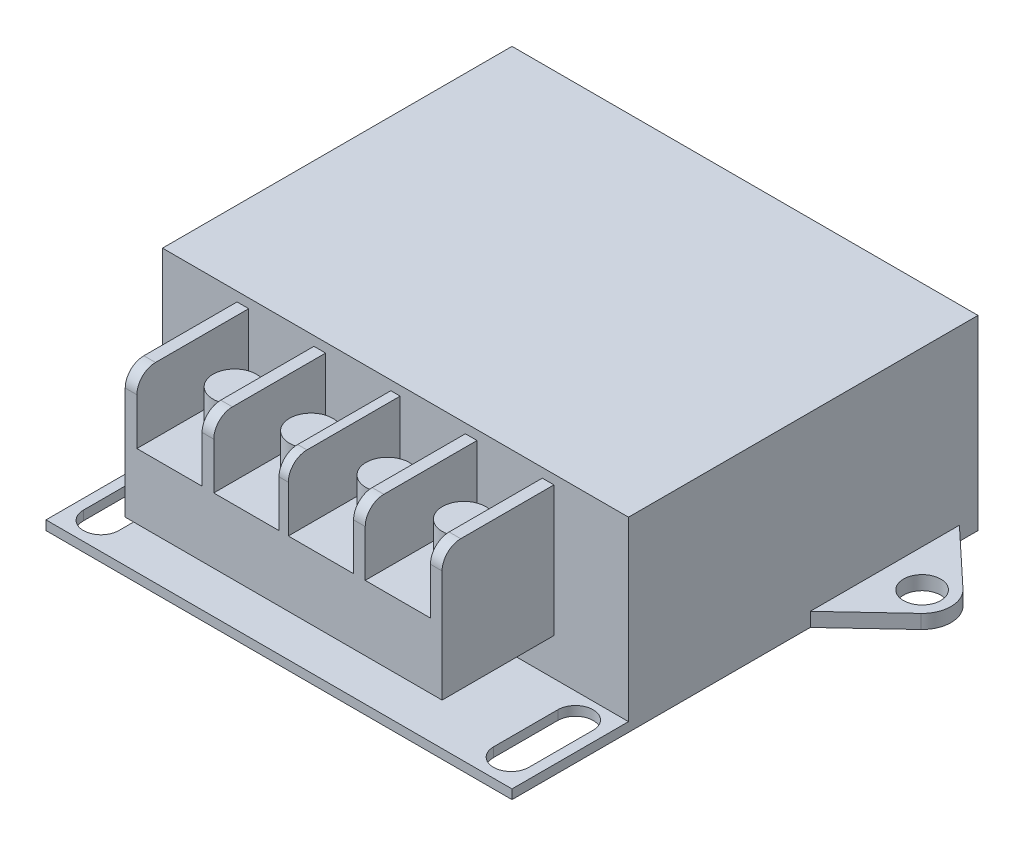
SolidWorks part; units mm, degrees
ref_plane "Front Plane" through (0, 0, 0) normal (0, 0, 1) x (1, 0, 0)
ref_plane "Top Plane" through (0, 0, 0) normal (0, 1, 0) x (1, 0, 0)
ref_plane "Right Plane" through (0, 0, 0) normal (1, 0, 0) x (0, 0, -1)
sketch "Sketch1" plane through (0, 0, 0) normal (0, 1, 0) x (1, 0, 0)
  line L1 (0, 0) -> (50, 0)
  line L2 (0, 0) -> (0, 50)
  line L3 (0, 50) -> (50, 50)
  line L4 (50, 0) -> (50, 50)
  dimension "D1" = 50
  dimension "D2" = 50
extrude "Boss-Extrude1" add sketch "Sketch1" along normal blind 1
sketch "Sketch2" plane through (0, 1, 0) normal (0, 1, 0) x (1, 0, 0)
  line L0 (50, 0) -> (50, 50) construction
  line L1 (0, 50) -> (50, 50)
  line L2 (0, 50) -> (0, 12.5)
  line L3 (0, 12.5) -> (50, 12.5)
  line L4 (50, 50) -> (50, 12.5)
  dimension "D1" = 37.5
extrude "Boss-Extrude2" add sketch "Sketch2" along normal blind 19
sketch "Sketch3" plane through (0, 0, -12.5) normal (0, 0, 1) x (1, 0, 0)
  line L0 (0, 20) -> (50, 20) construction
  line L1 (8, 19) -> (42, 19)
  line L2 (8, 19) -> (8, 5)
  line L3 (8, 5) -> (42, 5)
  line L4 (42, 19) -> (42, 5)
  point P4 (25, 20)
  point P5 (25, 19)
  dimension "D1" = 34
  dimension "D2" = 14
  dimension "D3" = 1
extrude "Boss-Extrude3" add sketch "Sketch3" along normal blind 12
sketch "Sketch4" plane through (0, 0, 0) normal (0, -1, 0) x (1, 0, 0)
  line L0 (0, -50) -> (0, 0) construction
  line L2 (-6.1215, -37.7396) -> (0, -32.0038)
  line L3 (-6.1215, -42.2679) -> (0, -48.0038)
  circle A0 centre (-4, -40.0038) radius 2
  arc A2 (-6.1215, -37.7396) -> (-6.1215, -42.2679) centre (-4, -40.0038) ccw
  point P4 (-7, -40.7957)
  line M6 (0, 0) -> (0, -50)
  dimension "D1" = 4
  dimension "D2" = 4
  dimension "D3" = 16
  dimension "D4" = 7
extrude "Boss-Extrude4" add sketch "Sketch4" against normal blind 1.5 contours L2 A2 L3 A0 M6 region at (-2.9411, 0, -34.9994)
ref_plane "Plane1" through (25, 0, 0) normal (-1, 0, 0) x (0, 0, 1)
mirror "Mirror1" about plane through (25, 0, 0) normal (-1, 0, 0) of "Boss-Extrude4"
sketch "Sketch5" plane through (0, 19, 0) normal (0, 1, 0) x (1, 0, 0)
  line L0 (42, 0.5) -> (8, 0.5) construction
  line L1 (9.25, 0.5) -> (16.25, 0.5)
  line L2 (9.25, 0.5) -> (9.25, 12.5)
  line L3 (9.25, 12.5) -> (16.25, 12.5)
  line L4 (16.25, 0.5) -> (16.25, 12.5)
  line L5 (8, 0.5) -> (8, 12.5) construction
  line L6 (17.5, 0.5) -> (24.5, 0.5)
  line L7 (17.5, 0.5) -> (17.5, 12.5)
  line L8 (17.5, 12.5) -> (24.5, 12.5)
  line L9 (24.5, 0.5) -> (24.5, 12.5)
  line L10 (25.5, 0.5) -> (32.5, 0.5)
  line L11 (25.5, 0.5) -> (25.5, 12.5)
  line L12 (25.5, 12.5) -> (32.5, 12.5)
  line L13 (32.5, 0.5) -> (32.5, 12.5)
  line L14 (33.75, 0.5) -> (40.75, 0.5)
  line L15 (33.75, 0.5) -> (33.75, 12.5)
  line L16 (33.75, 12.5) -> (40.75, 12.5)
  line L17 (40.75, 0.5) -> (40.75, 12.5)
  line L18 (42, 0.5) -> (42, 12.5) construction
  line L19 (0, 12.5) -> (50, 12.5) construction
  line M16 (42, 12.5) -> (8, 12.5)
  line M18 (8, 0.5) -> (42, 0.5)
  dimension "D1" = 7
  dimension "D2" = 1.25
  dimension "D3" = 1.25
  dimension "D4" = 1.25
  dimension "D5" = 1.25
extrude "Cut-Extrude1" cut sketch "Sketch5" against normal blind 7 contours L9 L7 M18 M16 | L13 L11 M18 M16 | L17 L15 M18 M16 | L1 L4 L3 L2 region at (21, 19, -6.5) region at (29, 19, -6.5) region at (37.25, 19, -6.5)
fillet "Fillet1" radius 2 5 edges at (41.375, 19, -0.5) (33.125, 19, -0.5) (25, 19, -0.5) (16.875, 19, -0.5) (8.625, 19, -0.5)
sketch "Sketch6" plane through (0, 12, 0) normal (0, 1, 0) x (1, 0, 0)
  line L0 (9.25, 0.5) -> (16.25, 0.5) construction
  line L1 (9.25, 2.5) -> (9.25, 12.5) construction
  circle A0 centre (12.75, 7.5) radius 2.3214
  point P2 (12.75, 0.5)
  point P6 (9.25, 7.5)
extrude "Boss-Extrude5" add sketch "Sketch6" along normal blind 4
pattern_linear "LPattern1" count 4 spacing 8.2 along (1, 0, 0) of "Boss-Extrude5"
sketch "Sketch7" plane through (0, 1, 0) normal (0, 1, 0) x (1, 0, 0)
  line L0 (3, 9.8115) -> (3, 2.9136) construction
  line L1 (4.9, 9.8115) -> (4.9, 2.9136)
  line L2 (1.1, 9.8115) -> (1.1, 2.9136)
  line L3 (47, 9.8115) -> (47, 2.9136) construction
  line L4 (48.9, 9.8115) -> (48.9, 2.9136)
  line L5 (45.1, 9.8115) -> (45.1, 2.9136)
  line L6 (0, 12.5) -> (0, 0) construction
  line L8 (50, 0) -> (50, 12.5) construction
  arc A0 (4.9, 9.8115) -> (1.1, 9.8115) centre (3, 9.8115) ccw
  arc A1 (1.1, 2.9136) -> (4.9, 2.9136) centre (3, 2.9136) ccw
  arc A2 (48.9, 9.8115) -> (45.1, 9.8115) centre (47, 9.8115) ccw
  arc A3 (45.1, 2.9136) -> (48.9, 2.9136) centre (47, 2.9136) ccw
  point P2 (3, 6.3625)
  point P7 (47, 6.3625)
  dimension "D1" = 1.9
  dimension "D2" = 3
  dimension "D3" = 3
extrude "Cut-Extrude2" cut sketch "Sketch7" against normal through all
